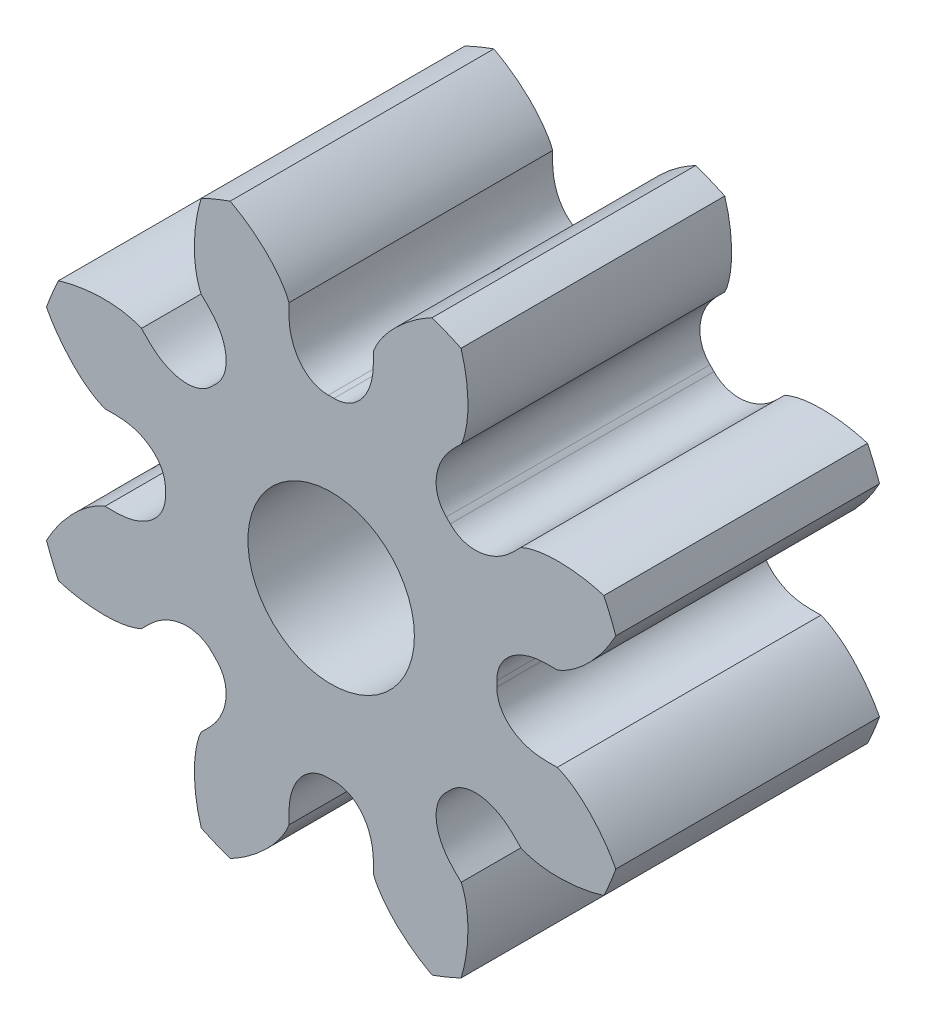
SolidWorks part; units mm, degrees
ref_plane "Front" through (0, 0, 0) normal (0, 0, 1) x (1, 0, 0)
ref_plane "Top" through (0, 0, 0) normal (0, 1, 0) x (1, 0, 0)
ref_plane "Right" through (0, 0, 0) normal (1, 0, 0) x (0, 0, -1)
sketch "Sketch3" plane through (0, 0, 0) normal (0, 0, 1) x (1, 0, 0)
  circle A0 centre (0, 0) radius 4.5357
  dimension "od" = 9.0714
extrude "gearBody" add sketch "Sketch3" along normal blind 3.96
sketch "Sketch2" plane through (0, 0, 0) normal (0, 0, 1) x (1, 0, 0)
  line L2 (0, 0) -> (36.3143, 0) construction
  line L3 (3.5578, 0.7133) -> (3.5578, -0.7133) construction
  line L5 (3.5578, 0) -> (0, 0) construction
  line L7 (0, 0) -> (3.4097, 0) construction
  line L8 (0, 0) -> (3.5578, -0.7133) construction
  arc A0 (3.3432, 0.6703) -> (3.3432, -0.6703) centre (0, 0) ccw construction
  arc A1 (4.4472, 0.8917) -> (4.4472, -0.8917) centre (0, 0) ccw construction
  arc A2 (3.5578, 0.7133) -> (3.5578, -0.7133) centre (0, 0) ccw construction
  arc A3 (2.4888, -0.0425) -> (2.4888, 0.0425) centre (0, 0) ccw
  arc A7 (4.4383, -1.8484) -> (4.4383, 1.8484) centre (0, 0) ccw
  spline S0 degree 3 poles (2.4888, -0.0425) (2.4888, -0.0507) (2.4888, -0.0879) (2.5001, -0.1773) (2.5591, -0.3297) (2.7372, -0.5204) (3.0436, -0.64) (3.2809, -0.6354) (3.3956, -0.6332) knots 0 0 0 0 0.020194 0.091808 0.221188 0.41692 0.7181 1 1 1 1
  spline S1 degree 3 poles (3.3956, -0.6332) (3.414, -0.6405) (3.4512, -0.6551) (3.5051, -0.6825) (3.6674, -0.7758) (3.9192, -0.9939) (4.2188, -1.3801) (4.363, -1.6877) (4.4383, -1.8484) knots 0 0 0 0 0.036273 0.073157 0.110648 0.379214 0.675729 1 1 1 1
  spline S2 degree 3 poles (2.4888, 0.0425) (2.4888, 0.0507) (2.4888, 0.0879) (2.5001, 0.1773) (2.5591, 0.3297) (2.7372, 0.5204) (3.0436, 0.64) (3.2809, 0.6354) (3.3956, 0.6332) knots 0 0 0 0 0.020194 0.091808 0.221188 0.41692 0.7181 1 1 1 1
  spline S3 degree 3 poles (3.3956, 0.6332) (3.414, 0.6405) (3.4512, 0.6551) (3.5051, 0.6825) (3.6674, 0.7758) (3.9192, 0.9939) (4.2188, 1.3801) (4.363, 1.6877) (4.4383, 1.8484) knots 0 0 0 0 0.036273 0.073157 0.110648 0.379214 0.675729 1 1 1 1
  point P6 (1.2223, 0.1469)
  point P22 (1.2223, -0.1469)
  dimension "baseDia" = 6.8195
  dimension "od" = 9.0714
  dimension "pd" = 7.2571
  dimension "rd" = 4.9784
  dimension "pointX" = 1.2223
  dimension "pointY" = 0.1469
  dimension "CTT" = 1.4267
  dimension "trE0" = 0.4476
  dimension "trR1" = 2.4899
  dimension "trE1" = 0.4236
  dimension "trR2" = 2.5044
  dimension "trE2" = 0.341
  dimension "trR3" = 2.5738
  dimension "trE3" = 0.2083
  dimension "trR4" = 2.7571
  dimension "trE4" = 0.0665
  dimension "trR5" = 3.1152
  dimension "trE5" = 0.0056
  dimension "trR6" = 3.4541
  dimension "trE6" = 0.0467
  dimension "ivR1" = 3.5123
  dimension "ivE1" = 0.0353
  dimension "ivR2" = 3.5704
  dimension "ivE2" = 0.0195
  dimension "ivR3" = 4.0217
  dimension "ivE3" = 0.2075
  dimension "ivR4" = 4.4148
  dimension "ivE4" = 0.5252
  dimension "ivR5" = 4.8079
  dimension "ivE5" = 0.9398
extrude "toothCut" cut sketch "Sketch2" along normal through all
pattern_circular "CirPattern1" count 8 over 360 about axis through (0, 0, 3.96) along (0, 0, -1) of "toothCut"
ref_axis "toothSpace" through (0, 0, 0) along (1, 0, 0)
sketch "boreDia" plane through (0, 0, 0) normal (0, 0, 1) x (1, 0, 0)
  circle A0 centre (0, 0) radius 1.25
  dimension "boreDia" = 2.5
extrude "bore" cut sketch "boreDia" against normal mid plane 25400
sketch "kwy2sketch" plane through (0, 0, 0) normal (0, 0, 1) x (1, 0, 0)
  line L0 (2.4892, 0) -> (0, 0) construction
  line L1 (0, 0) -> (-3.1713, -1.8309) construction
  line L2 (1.6986, 1.558) -> (2.1986, 0.692)
  line L3 (2.1986, 0.692) -> (1.116, 0.067)
  line L4 (1.6986, 1.558) -> (0.616, 0.933)
  line L5 (1.116, 0.067) -> (0, 0)
  line L6 (0, 0) -> (0.616, 0.933)
  arc A2 (2.4888, -0.0425) -> (2.4888, 0.0425) centre (0, 0) ccw construction
  point P10 (1.9486, 1.125)
  dimension "kwy2angle" = 30
  dimension "kwy2Width" = 1
  dimension "kwy2depth" = 2.25
  dimension "kwy2Depth2" = 1.25
extrude "kwy2" [suppressed] cut sketch "kwy2sketch" against normal mid plane 12700
sketch "centerLine" plane through (0, 0, 0) normal (0, 1, 0) x (1, 0, 0)
  line L0 (0, 36.4807) -> (0, -59.6309) construction
ref_plane "CB1plane" through (0, 0, 0) normal (0, 0, -1) x (-1, 0, 0)
ref_plane "CB2plane" through (0, 0, 3.96) normal (0, 0, 1) x (1, 0, 0)
ref_axis "Axis1" through (0, 0, 50) along (0, 0, -1)
sketch3d "3DSketch1" plane through (0, 0, 0) normal (0, 0, 1) x (1, 0, 0)
